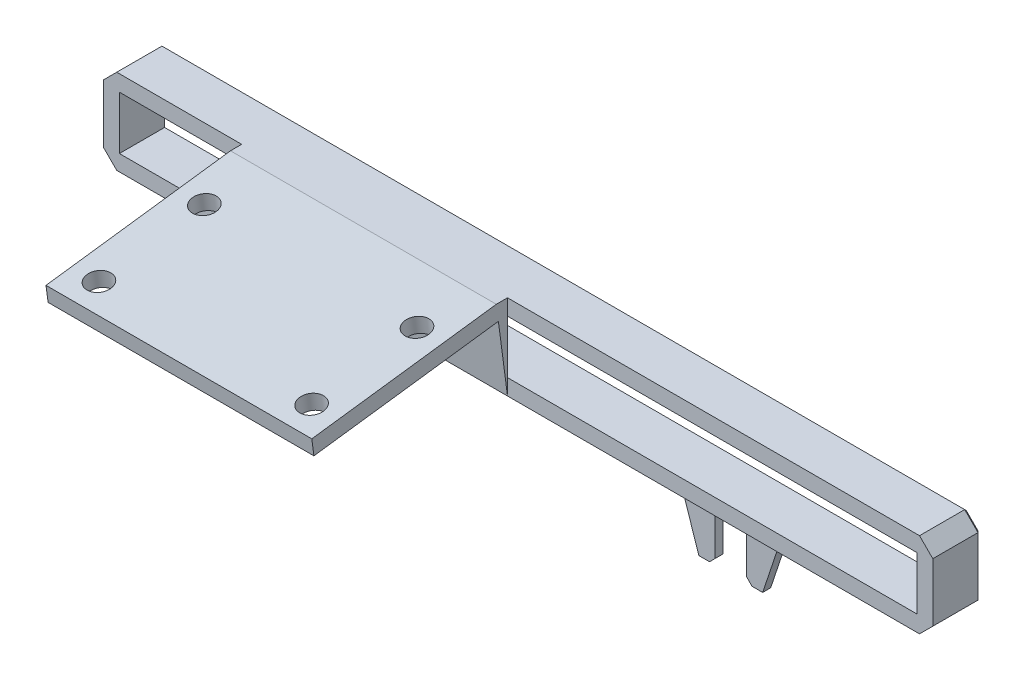
SolidWorks part; units mm, degrees
ref_plane "Top Plane" through (0, 0, 0) normal (0, 0, 1) x (1, 0, 0)
ref_plane "Front Plane" through (0, 0, 0) normal (0, 1, 0) x (1, 0, 0)
ref_plane "Right Plane" through (0, 0, 0) normal (1, 0, 0) x (0, 0, -1)
sketch "Sketch1" plane through (0, 0, 0) normal (0, 0, 1) x (1, 0, 0)
  line L1 (0, 0) -> (156, 0)
  line L2 (0, 0) -> (0, 16)
  line L3 (0, 16) -> (156, 16)
  line L4 (156, 0) -> (156, 16)
  dimension "D1" = 156
  dimension "D2" = 16
extrude "Boss-Extrude1" add sketch "Sketch1" along normal blind 9
sketch "Sketch2" plane through (0, 0, 9) normal (0, 0, 1) x (1, 0, 0)
  line L14 (153, 3) -> (153, 13)
  line L15 (3, 3) -> (153, 3)
  line L16 (3, 13) -> (3, 3)
  line L17 (153, 13) -> (3, 13)
  line L18 (153, 3) -> (153, 13)
  line L19 (3, 3) -> (153, 3)
  line L20 (3, 13) -> (3, 3)
  line L21 (153, 13) -> (3, 13)
  dimension "D1" = 3
extrude "Cut-Extrude1" cut sketch "Sketch2" against normal blind 9
sketch "Sketch4" plane through (156, 0, 0) normal (1, 0, 0) x (0, 0, -1)
  line L0 (-9, 16) -> (-11.1064, 16)
  line L1 (-11.1064, 16) -> (-9, 0)
  line L2 (-9, 0) -> (-9, 16)
  dimension "D1" = 7.5
extrude "Boss-Extrude2" add sketch "Sketch4" along normal blind 50 from offset 130 offset against normal yes
sketch "Sketch5" plane through (0, -1.1647, 8.8467) normal (0, -0.1305, 0.9914) x (1, 0, 0)
  line L0 (76, 17.3128) -> (76, 1.1747) construction
  line L1 (26, 17.3128) -> (76, 17.3128)
  line L2 (26, 17.3128) -> (26, 14.3128)
  line L3 (26, 14.3128) -> (76, 14.3128)
  line L4 (76, 17.3128) -> (76, 14.3128)
  line L6 (76, 17.3128) -> (26, 17.3128) construction
  line L7 (26, 17.3128) -> (26, 1.1747) construction
  dimension "D1" = 3
extrude "Boss-Extrude3" add sketch "Sketch5" along normal blind 35
sketch "Sketch6" plane through (0, 17.1647, 2.2598) normal (0, 0.9914, 0.1305) x (1, 0, 0)
  line L0 (76, -8.923) -> (26, -8.923) construction
  line L1 (31, -18.923) -> (71, -18.923)
  line L2 (31, -18.923) -> (31, -38.923)
  line L3 (31, -38.923) -> (71, -38.923)
  line L4 (71, -18.923) -> (71, -38.923)
  line L5 (26, -43.923) -> (26, -8.923) construction
  dimension "D1" = 40
  dimension "D2" = 20
  dimension "D3" = 10
  dimension "D4" = 5
hole_wizard "M4 Clearance Hole1" positions "Sketch7" profile "Sketch8" hole size "M4" standard "DIN" end condition through all
sketch "Sketch7" plane through (0, 17.1647, 2.2598) normal (0, 0.9914, 0.1305) x (1, 0, 0)
  point P0 (31, -18.923)
  point P3 (71, -18.923)
  point P6 (71, -38.923)
  point P9 (31, -38.923)
sketch "Sketch8" plane through (31, 14.6947, 21.0209) normal (1, 0, 0) x (0, -0.1305, 0.9914)
  line L0 (0, 0) -> (0, 17.3128)
  line L1 (0, 17.3128) -> (2.25, 17.3128)
  line L2 (2.25, 17.3128) -> (2.25, 0)
  line L5 (2.25, 0) -> (0, 0)
  line L11 (0, -6.35) -> (0, 107.95) construction
  dimension "Thru Hole Dia." = 4.5
  dimension "Thru Hole Depth" = 17.3128
sketch "Sketch10" plane through (0, 0, 0) normal (0, -1, 0) x (1, 0, 0)
  line L0 (0, 0) -> (156, 0) construction
  line L1 (105, 2) -> (117, 2)
  line L2 (105, 2) -> (105, 0)
  line L3 (105, 0) -> (117, 0)
  line L4 (117, 2) -> (117, 0)
  line L5 (156, 9) -> (156, 0) construction
  dimension "D1" = 2
  dimension "D2" = 12
  dimension "D3" = 39
extrude "Boss-Extrude4" add sketch "Sketch10" along normal blind 15
sketch "Sketch11" plane through (0, 0, 0) normal (0, 0, -1) x (-1, 0, 0)
  line L0 (-105, -15) -> (-117, -15) construction
  line L1 (-114, -15) -> (-108, -15)
  line L2 (-114, -15) -> (-114, -4)
  line L3 (-114, -4) -> (-108, -4)
  line L4 (-108, -15) -> (-108, -4)
  line L5 (0, 0) -> (-105, 0) construction
  line L6 (-105, -15) -> (-105, 0) construction
  dimension "D1" = 6
  dimension "D2" = 4
  dimension "D3" = 3
extrude "Cut-Extrude2" cut sketch "Sketch11" against normal blind 15
chamfer "Chamfer1" distance 5 distance2 15 2 edges at (117, 0, 1) (105, 0, 1) first distance on face at (85.8, 0, 4)
chamfer "Chamfer2" distance 1 angle 45 2 edges at (108, -15, 1) (114, -15, 1)
chamfer "Chamfer3" distance 2.5 angle 45 4 edges at (0, 0, 4.5) (0, 16, 4.5) (156, 16, 4.5) (156, 0, 4.5)
chamfer "Chamfer4" distance 2 angle 45 1 edges at (111, 0, 2)
chamfer "Chamfer5" distance 0.5 angle 45 22 edges at (3, 8, 0) (78, 13, 0) (153, 8, 0) (78, 3, 0) (102.5, -7.5, 0) (106, -15, 0) (107.5, -14.5, 0) (108, -9, 0) (111, -4, 0) (114, -9, 0) (114.5, -14.5, 0) (116, -15, 0) (119.5, -7.5, 0) (137.75, 0, 0) (154.75, 1.25, 0) (156, 8, 0) (154.75, 14.75, 0) (78, 16, 0) (1.25, 14.75, 0) (0, 8, 0) (1.25, 1.25, 0) (51.25, 0, 0)
